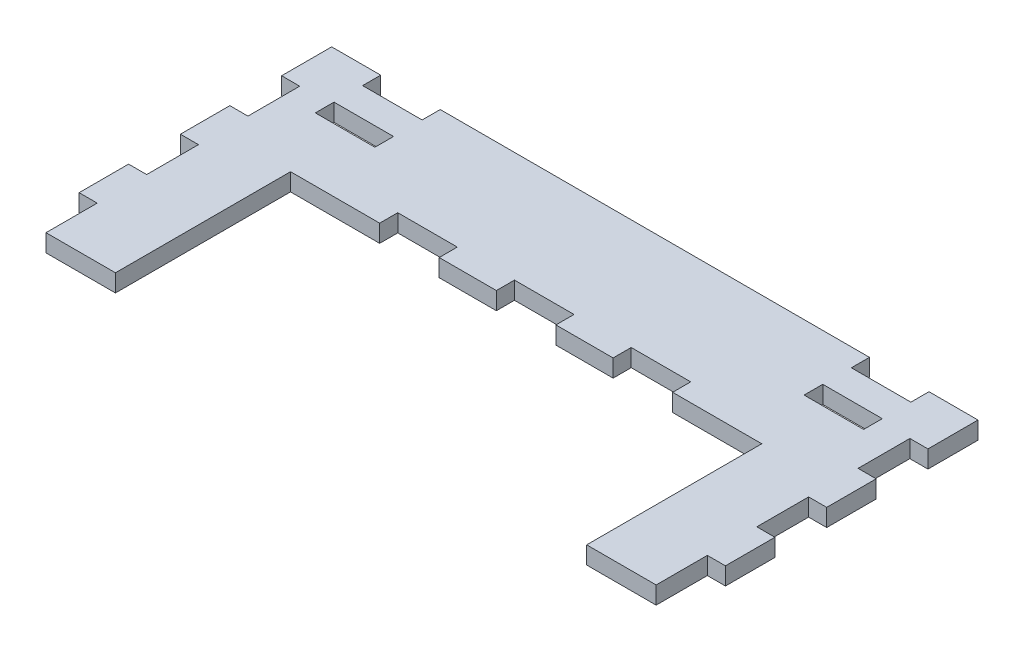
SolidWorks part; units mm, degrees
ref_plane "Front Plane" through (0, 0, 0) normal (0, 0, 1) x (1, 0, 0)
ref_plane "Top Plane" through (0, 0, 0) normal (0, 1, 0) x (1, 0, 0)
ref_plane "Right Plane" through (0, 0, 0) normal (1, 0, 0) x (0, 0, -1)
sketch "Sketch1" plane through (0, 0, 0) normal (0, 1, 0) x (1, 0, 0)
  line L0 (0, 0) -> (0, 52.05) construction
  line L1 (-55.3722, 52.05) -> (55.3722, 52.05)
  line L2 (-55.3722, 52.05) -> (-55.3722, 0)
  line L3 (-55.3722, 0) -> (55.3722, 0) construction
  line L4 (55.3722, 52.05) -> (55.3722, 0)
  line L6 (40.3722, 0) -> (40.3722, 30)
  line L7 (40.3722, 30) -> (-40.3722, 30)
  line L8 (-40.3722, 30) -> (-40.3722, 0)
  line L9 (55.3722, 0) -> (40.3722, 0)
  line L10 (-40.3722, 0) -> (-55.3722, 0)
  dimension "D1" = 15
sketch "Sketch2" plane through (0, 0, 0) normal (1, 0, 0) x (0, 0, -1)
  line L1 (0, 0) -> (52.05, 0)
  line L2 (0, 0) -> (0, 3)
  line L3 (0, 3) -> (52.05, 3)
  line L4 (52.05, 0) -> (52.05, 3)
extrude "Boss-Extrude1" add sketch "Sketch1" along normal up to vertex (3 mm away) up to point (0, 3, -52.05)
sketch "Sketch3" plane through (0, 0, 0) normal (0, 1, 0) x (1, 0, 0)
  line L0 (55.3722, 52.05) -> (55.3722, 0) construction
  line L1 (55.3722, 0) -> (40.3722, 0) construction
  line L2 (40.3722, 0) -> (40.3722, 30) construction
  line L3 (40.3722, 30) -> (-40.3722, 30) construction
  line L4 (-40.3722, 30) -> (-40.3722, 0) construction
  line L5 (-40.3722, 0) -> (-55.3722, 0) construction
  line L6 (-55.3722, 52.05) -> (-55.3722, 0) construction
  line L7 (-55.3722, 52.05) -> (55.3722, 52.05) construction
  line L8 (55.3722, 52.05) -> (55.3722, 0) construction
  line L9 (55.3722, 0) -> (40.3722, 0) construction
  line L10 (40.3722, 0) -> (40.3722, 30) construction
  line L11 (40.3722, 30) -> (-40.3722, 30) construction
  line L12 (-40.3722, 30) -> (-40.3722, 0) construction
  line L13 (-40.3722, 0) -> (-55.3722, 0) construction
  line L14 (-55.3722, 52.05) -> (-55.3722, 0) construction
  line L15 (-55.3722, 52.05) -> (55.3722, 52.05) construction
  line L16 (36.8722, 52.05) -> (36.8722, 30) construction
  line L17 (-36.8722, 52.05) -> (-36.8722, 30) construction
  line L18 (55.3722, 49.05) -> (-55.3722, 49.05) construction
  line L19 (55.3722, 40.95) -> (-55.3722, 40.95) construction
  line L20 (55.3722, 43.95) -> (-55.3722, 43.95) construction
  line L21 (-55.3722, 33) -> (55.3722, 33) construction
  line L22 (52.3722, 52.05) -> (52.3722, 0) construction
  line L23 (-52.3722, 52.05) -> (-52.3722, 0) construction
  line L24 (0, 52.05) -> (0, 0) construction
  line L25 (46.8722, 52.05) -> (46.8722, 49.05) construction
  line L26 (46.8722, 43.95) -> (46.8722, 40.95) construction
  line L27 (40.3722, 30) -> (55.3722, 30) construction
  line L28 (-40.3722, 30) -> (-55.3722, 30) construction
  line L30 (35, 33) -> (35, 30) construction
  line L33 (25, 33) -> (25, 30) construction
  line L34 (25, 31.5) -> (35, 31.5) construction
  line L35 (5, 33) -> (5, 30) construction
  line L36 (5, 31.5) -> (-5, 31.5) construction
  line L37 (25, 31.5) -> (15, 31.5) construction
  line L38 (15, 31.5) -> (5, 31.5) construction
  line L39 (15, 33) -> (15, 30) construction
  line L43 (52.3722, 43.375) -> (55.3722, 43.375) construction
  line L44 (55.3722, 34.7) -> (52.3722, 34.7) construction
  line L45 (53.8722, 34.7) -> (53.8722, 43.375) construction
  line L46 (53.8722, 43.375) -> (53.8722, 52.05) construction
  line L47 (53.8722, 34.7) -> (53.8722, 26.025) construction
  line L48 (55.3722, 26.025) -> (52.3722, 26.025) construction
  line L49 (55.3722, 17.35) -> (52.3722, 17.35) construction
  line L50 (53.8722, 26.025) -> (53.8722, 17.35) construction
  line L51 (55.3722, 8.675) -> (52.3722, 8.675) construction
  line L52 (53.8722, 17.35) -> (53.8722, 8.675) construction
  line L53 (53.8722, 8.675) -> (53.8722, 0) construction
  dimension "D1" = 10
  dimension "D2" = 8.675
  dimension "D3" = 10
sketch "Sketch4" plane through (0, 0, 0) normal (0, 1, 0) x (1, 0, 0)
  line L0 (0, 0) -> (0, 52.05) construction
  line L1 (46.9722, 52.15) -> (36.7722, 52.15)
  line L2 (46.9722, 52.15) -> (46.9722, 48.95)
  line L3 (46.9722, 48.95) -> (36.7722, 48.95)
  line L4 (36.7722, 52.15) -> (36.7722, 48.95)
  line L5 (46.9722, 44.05) -> (36.7722, 44.05)
  line L6 (46.9722, 44.05) -> (46.9722, 40.85)
  line L7 (46.9722, 40.85) -> (36.7722, 40.85)
  line L8 (36.7722, 44.05) -> (36.7722, 40.85)
  line L9 (55.4722, 43.475) -> (52.2722, 43.475)
  line L10 (55.4722, 43.475) -> (55.4722, 34.6)
  line L11 (55.4722, 34.6) -> (52.2722, 34.6)
  line L12 (52.2722, 43.475) -> (52.2722, 34.6)
  line L13 (55.4722, 26.125) -> (52.2722, 26.125)
  line L14 (55.4722, 26.125) -> (55.4722, 17.25)
  line L15 (55.4722, 17.25) -> (52.2722, 17.25)
  line L16 (52.2722, 26.125) -> (52.2722, 17.25)
  line L17 (55.4722, 8.775) -> (52.2722, 8.775)
  line L18 (55.4722, 8.775) -> (55.4722, -0.1)
  line L19 (55.4722, -0.1) -> (52.2722, -0.1)
  line L20 (52.2722, 8.775) -> (52.2722, -0.1)
  line L21 (20, 33.1) -> (20, 33) construction
  line L22 (20, 29.9) -> (20, 30) construction
  line L23 (40.3722, 30) -> (-40.3722, 30) construction
  line L24 (-55.3722, 33) -> (55.3722, 33) construction
  line L25 (25.1, 33.1) -> (14.9, 33.1)
  line L26 (25.1, 33.1) -> (25.1, 29.9)
  line L27 (25.1, 29.9) -> (14.9, 29.9)
  line L28 (14.9, 33.1) -> (14.9, 29.9)
  line L29 (5.1, 33.1) -> (-5.1, 33.1)
  line L30 (5.1, 33.1) -> (5.1, 29.9)
  line L31 (5.1, 29.9) -> (-5.1, 29.9)
  line L32 (-5.1, 33.1) -> (-5.1, 29.9)
  line L33 (0, 0) -> (0, 52.05) construction
  line L34 (41.8722, 52.15) -> (41.8722, 52.05) construction
  line L35 (41.8722, 48.95) -> (41.8722, 49.05) construction
  line L36 (36.7722, 50.55) -> (36.8722, 50.55) construction
  line L37 (46.9722, 50.55) -> (46.8722, 50.55) construction
  line L38 (46.8722, 52.05) -> (46.8722, 49.05) construction
  line L39 (-55.3722, 52.05) -> (55.3722, 52.05) construction
  line L40 (55.3722, 49.05) -> (-55.3722, 49.05) construction
  line L41 (36.8722, 52.05) -> (36.8722, 30) construction
  line L42 (52.2722, 39.0375) -> (52.3722, 39.0375) construction
  line L43 (55.4722, 39.0375) -> (55.3722, 39.0375) construction
  line L44 (53.8722, 43.475) -> (53.8722, 43.375) construction
  line L45 (53.8722, 34.6) -> (53.8722, 34.7) construction
  line L46 (53.8722, 26.125) -> (53.8722, 26.025) construction
  line L47 (53.8722, 17.25) -> (53.8722, 17.35) construction
  line L48 (53.8722, 8.775) -> (53.8722, 8.675) construction
  line L49 (53.8722, -0.1) -> (53.8722, 0) construction
  line L50 (41.8722, 44.05) -> (41.8722, 43.95) construction
  line L51 (41.8722, 40.85) -> (41.8722, 40.95) construction
  line L52 (55.3722, 43.95) -> (-55.3722, 43.95) construction
  line L53 (55.3722, 40.95) -> (-55.3722, 40.95) construction
  line L54 (52.3722, 43.375) -> (55.3722, 43.375) construction
  line L55 (55.3722, 34.7) -> (52.3722, 34.7) construction
  line L56 (52.3722, 52.05) -> (52.3722, 0) construction
  line L57 (55.3722, 52.05) -> (55.3722, 0) construction
  line L58 (55.3722, 26.025) -> (52.3722, 26.025) construction
  line L59 (55.3722, 17.35) -> (52.3722, 17.35) construction
  line L60 (55.3722, 0) -> (40.3722, 0) construction
  line L61 (55.3722, 8.675) -> (52.3722, 8.675) construction
  line L70 (25.1, 31.5) -> (25, 31.5) construction
  line L71 (14.9, 31.5) -> (15, 31.5) construction
  line L72 (5.1, 31.5) -> (5, 31.5) construction
  line L73 (5, 33) -> (5, 30) construction
  line L74 (15, 33) -> (15, 30) construction
  line L75 (25, 33) -> (25, 30) construction
  line L76 (-55.4722, 8.775) -> (-52.2722, 8.775)
  line L77 (-55.4722, 8.775) -> (-55.4722, -0.1)
  line L78 (-55.4722, -0.1) -> (-52.2722, -0.1)
  line L79 (-52.2722, 8.775) -> (-52.2722, -0.1)
  line L80 (-55.4722, 26.125) -> (-52.2722, 26.125)
  line L81 (-55.4722, 26.125) -> (-55.4722, 17.25)
  line L82 (-55.4722, 17.25) -> (-52.2722, 17.25)
  line L83 (-52.2722, 26.125) -> (-52.2722, 17.25)
  line L84 (-55.4722, 43.475) -> (-52.2722, 43.475)
  line L85 (-55.4722, 43.475) -> (-55.4722, 34.6)
  line L86 (-55.4722, 34.6) -> (-52.2722, 34.6)
  line L87 (-52.2722, 43.475) -> (-52.2722, 34.6)
  line L88 (-46.9722, 52.15) -> (-46.9722, 48.95)
  line L89 (-46.9722, 52.15) -> (-36.7722, 52.15)
  line L90 (-36.7722, 52.15) -> (-36.7722, 48.95)
  line L91 (-46.9722, 48.95) -> (-36.7722, 48.95)
  line L92 (-46.9722, 44.05) -> (-46.9722, 40.85)
  line L93 (-46.9722, 40.85) -> (-36.7722, 40.85)
  line L94 (-36.7722, 44.05) -> (-36.7722, 40.85)
  line L95 (-46.9722, 44.05) -> (-36.7722, 44.05)
  line L100 (-25.1, 33.1) -> (-25.1, 29.9)
  line L101 (-25.1, 29.9) -> (-14.9, 29.9)
  line L102 (-14.9, 33.1) -> (-14.9, 29.9)
  line L103 (-25.1, 33.1) -> (-14.9, 33.1)
  dimension "D1" = 0.1
extrude "Cut-Extrude1" cut sketch "Sketch4" along normal through all
